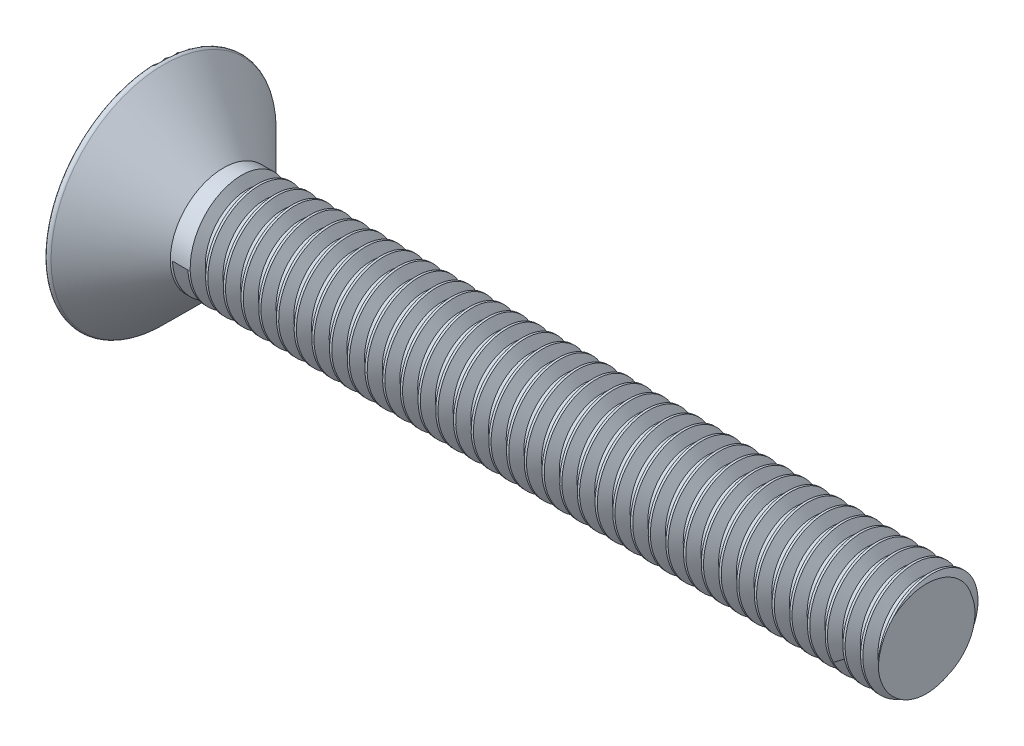
SolidWorks part; units mm, degrees
ref_plane "Front Plane" through (0, 0, 0) normal (0, 0, 1) x (1, 0, 0)
ref_plane "Top Plane" through (0, 0, 0) normal (0, 1, 0) x (1, 0, 0)
ref_plane "Right Plane" through (0, 0, 0) normal (1, 0, 0) x (0, 0, -1)
sketch "Sketch1" plane through (0, 0, 0) normal (0, 1, 0) x (1, 0, 0)
  line L0 (-8.5891, 0) -> (8.9417, 0) construction
  line L1 (-6.5237, 0) -> (-6.5237, 3.35)
  line L2 (-6.5237, 3.35) -> (-4.6637, 1.5)
  line L3 (-4.6637, 1.5) -> (15.3363, 1.5)
  line L4 (15.3363, 1.5) -> (15.3363, 0)
  line L5 (15.3363, 0) -> (-6.5237, 0)
  dimension "D1" = 6.7
  dimension "D2" = 3
  dimension "D3" = 20
  dimension "D4" = 1.86
revolve "Revolve1" add sketch "Sketch1" angle 360 about L0
fillet "Fillet1" radius 0.1 1 edges at (-6.5237, 0, 3.35)
thread "Thread1" pitch 0.5 method cut profile "Thread Profile2" start angle 0, offset 0.5, length 20, pitch 0.5, diameter 3
ref_plane "Plane2" through (15.8363, 0, 1.5) normal (0, -1, 0) x (0, 0, 1)
sketch "Thread Profile2" plane through (15.8363, 0, 1.5) normal (0, -1, 0) x (0, 0, 1)
  line L0 (0, 0) -> (0, 0.5) construction
  line L11 (0, 0) -> (0, 0.4375)
  line L12 (0, 0.4375) -> (-0.2706, 0.2812)
  line L13 (-0.2706, 0.2812) -> (-0.2706, 0.1562)
  line L15 (-0.2706, 0.1562) -> (0, 0)
  line L17 (-0.2706, 0.2187) -> (0, 0.2187) construction
  point P2 (0, 0)
  dimension "Pitch" = 0.5
  dimension "Profile_Angle" = 60
  dimension "Profile_Land" = 0.125
  dimension "Profile_Height" = 0.2706
sketch "Sketch6" plane through (-6.5237, 0, 0) normal (-1, 0, 0) x (0, 0, 1)
  line L1 (1.1547, 0) -> (0.5774, 1)
  line L2 (0.5774, 1) -> (-0.5774, 1)
  line L3 (-0.5774, 1) -> (-1.1547, 0)
  line L4 (-1.1547, 0) -> (-0.5774, -1)
  line L5 (-0.5774, -1) -> (0.5774, -1)
  line L6 (0.5774, -1) -> (1.1547, 0)
  circle A0 centre (0, 0) radius 1 construction
  dimension "D1" = 2
extrude "Cut-Extrude1" cut sketch "Sketch6" against normal blind 1.5
